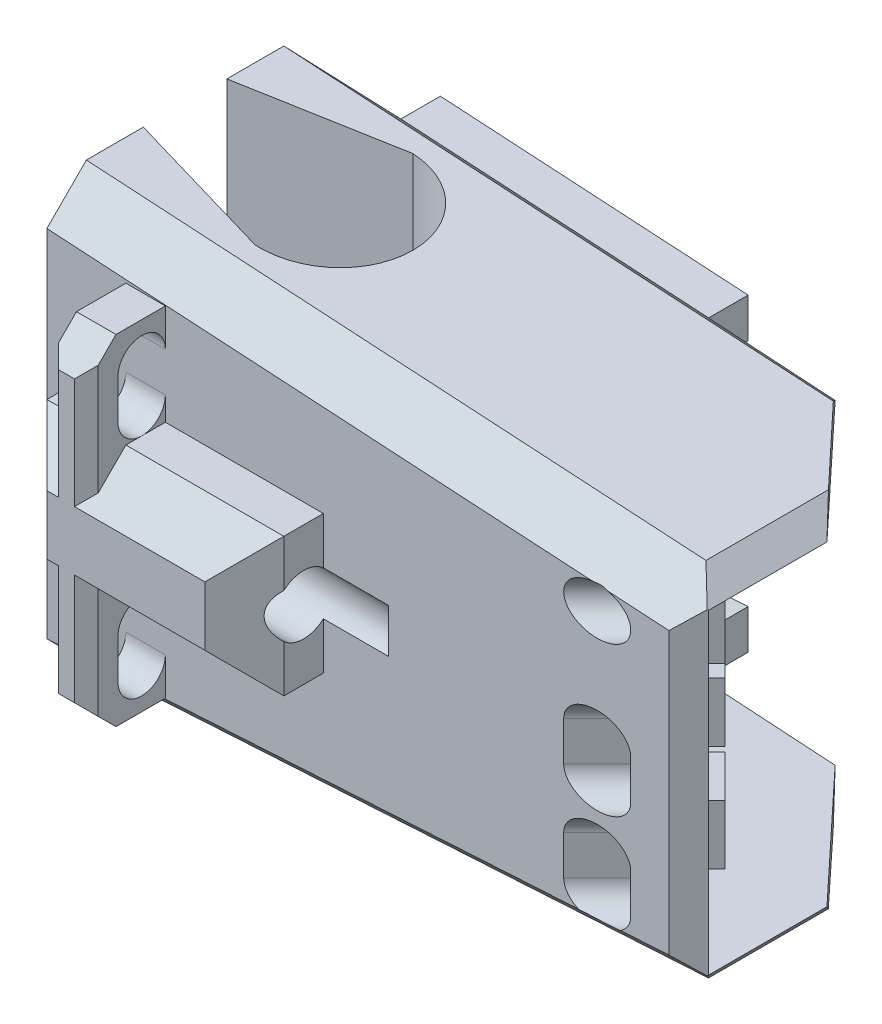
SolidWorks part; units mm, degrees
ref_plane "Front Plane" through (0, 0, 0) normal (0, 0, 1) x (1, 0, 0)
ref_plane "Top Plane" through (0, 0, 0) normal (0, 1, 0) x (1, 0, 0)
ref_plane "Right Plane" through (0, 0, 0) normal (1, 0, 0) x (0, 0, -1)
sketch "Sketch2" plane through (0, 0, 0) normal (0, 0, 1) x (1, 0, 0)
  line L0 (0, 0) -> (0, 11)
  line L1 (0, 11) -> (16.75, 10)
  line L2 (16.75, 10) -> (16.75, 1)
  line L3 (16.75, 1) -> (0, 0)
  dimension "D1" = 9
  dimension "D2" = 11
  dimension "D3" = 16.75
extrude "Boss-Extrude1" add sketch "Sketch2" along normal blind 7
chamfer "Chamfer1" distance 1 angle 45 4 edges at (8.375, 10.5, 0) (8.375, 0.5, 0) (8.375, 0.5, 7) (8.375, 10.5, 7)
chamfer "Chamfer7" distance 1 angle 45 4 edges at (16.75, 5.5, 7) (16.75, 1, 3.5) (16.75, 5.5, 0) (16.75, 10, 3.5)
chamfer "Chamfer14" distance 1 angle 63 1 edges at (0, 5.5, 0)
sketch "Sketch13" plane through (0, 0, 7) normal (0, 0, 1) x (1, 0, 0)
  line L0 (0, 5.5) -> (15.75, 5.5) construction
  line L1 (0, 9.9982) -> (0, 1.0018) construction
  line L2 (15.75, 1.9421) -> (15.75, 9.0579) construction
  line L3 (1, 3.75) -> (7, 3.75)
  line L5 (1, 3.75) -> (1, 7.25)
  line L6 (1, 7.25) -> (7, 7.25)
  line L7 (7, 3.75) -> (7, 7.25)
  point P11 (7, 5.5)
  point P12 (1, 5.5)
  dimension "D1" = 1.75
  dimension "D2" = 6
  dimension "D3" = 1
extrude "Boss-Extrude4" add sketch "Sketch13" along normal blind 2
sketch "Sketch14" plane through (1, 0, 0) normal (-1, 0, 0) x (0, 0, 1)
  line L0 (9, 5.5) -> (7, 5.5) construction
  line L1 (9, 7.25) -> (9, 3.75) construction
  line L2 (7, 7.25) -> (7, 3.75) construction
  circle A0 centre (7.5, 5.5) radius 0.75
  dimension "D1" = 1.5
  dimension "D2" = 1.5
extrude "Cut-Extrude9" cut sketch "Sketch14" against normal blind 7.6473 and the other way blind 2
chamfer "Chamfer15" distance 1 angle 45 4 edges at (4, 3.75, 9) (1, 5.5, 9) (4, 7.25, 9) (7, 5.5, 9)
sketch "Sketch15" plane through (0, 0, 0) normal (0, 0, -1) x (-1, 0, 0)
  line L0 (-1.9626, 5.5) -> (-15.75, 5.5) construction
  line L1 (-1.9626, 1.119) -> (-1.9626, 9.881) construction
  line L2 (-15.75, 9.0579) -> (-15.75, 1.9421) construction
  line L3 (-2.9626, 3.75) -> (-6.9626, 3.75)
  line L5 (-2.9626, 3.75) -> (-2.9626, 7.25)
  line L6 (-2.9626, 7.25) -> (-6.9626, 7.25)
  line L7 (-6.9626, 3.75) -> (-6.9626, 7.25)
  point P11 (-2.9626, 5.5)
  point P12 (-6.9626, 5.5)
  dimension "D1" = 1.75
  dimension "D2" = 1
  dimension "D3" = 4
extrude "Boss-Extrude6" add sketch "Sketch15" along normal blind 2
sketch "Sketch18" plane through (2.9626, 0, 0) normal (-1, 0, 0) x (0, 0, 1)
  line L0 (-2, 5.5) -> (0, 5.5) construction
  line L1 (-2, 3.75) -> (-2, 7.25) construction
  line L2 (0, 3.75) -> (0, 7.25) construction
  circle A0 centre (-0.5, 5.5) radius 0.75
  dimension "D1" = 1.5
  dimension "D2" = 1.5
extrude "Cut-Extrude10" cut sketch "Sketch18" against normal blind 6 and the other way blind 2
chamfer "Chamfer16" distance 1 angle 45 4 edges at (4.9626, 7.25, -2) (2.9626, 5.5, -2) (4.9626, 3.75, -2) (6.9626, 5.5, -2)
ref_plane "Plane1" through (4.875, 0, -4.875) normal (0.7071, 0, -0.7071) x (-0.7071, 0, -0.7071)
sketch "Sketch19" plane through (0, 0, 0) normal (0, 0, -1) x (-1, 0, 0)
  line L0 (-15.75, 5.5) -> (1.3235, 5.5) construction
  line L1 (-15.75, 9.0579) -> (-15.75, 1.9421) construction
  line L2 (-9.7553, 9.5) -> (-17.4165, 9.5)
  line L4 (-9.7553, 9.5) -> (-9.7553, 1.5)
  line L5 (-9.7553, 1.5) -> (-17.4165, 1.5)
  line L6 (-17.4165, 9.5) -> (-17.4165, 1.5)
  point P9 (-17.4165, 5.5)
  point P10 (-9.7553, 5.5)
  dimension "D1" = 4
extrude "Cut-Extrude12" cut sketch "Sketch19" against normal up to surface (0.0053 mm away) up to plane "Plane1"
sketch "Sketch21" plane through (0, 9.5, 0) normal (0, -1, 0) x (1, 0, 0)
  line L0 (16.25, 3.5) -> (16.25, 0.5)
  line L1 (16.25, 0.5) -> (16.25, 6.5) construction
  line L2 (16.25, 0.5) -> (16.25, -4.0591)
  line L3 (16.25, -4.0591) -> (11.3071, -4.0591)
  line L4 (11.3071, -4.0591) -> (13.25, 0.2923)
  line L5 (9.839, 0.089) -> (16.2193, 0.4693) construction
  line L6 (13.25, 0.2923) -> (16.25, 3.5)
  dimension "D1" = 3
extrude "Cut-Extrude14" cut sketch "Sketch21" against normal blind 2 and the other way blind 10
sketch "Sketch23" plane through (4.875, 0, -4.875) normal (0.7071, 0, -0.7071) x (-0.7071, 0, -0.7071)
  line L0 (-6.9018, 5.5) -> (-16.0867, 5.5009) construction
  line L1 (-6.9018, 9.4211) -> (-6.9018, 1.5789) construction
  line L2 (-16.0867, 1.5019) -> (-16.0867, 9.5) construction
  line L3 (-11.5534, 9.5) -> (-11.5522, 1.5) construction
  line L4 (-16.0867, 9.5) -> (-7.0202, 9.5) construction
  line L5 (-7.0202, 1.5) -> (-16.0843, 1.5) construction
  line L6 (-10.4024, 2.5007) -> (-10.4021, 4.0007)
  line L7 (-8.9018, 8.5) -> (-10.4018, 8.5)
  line L8 (-8.9018, 8.5) -> (-8.9018, 7)
  line L9 (-8.9018, 7) -> (-10.4018, 7)
  line L10 (-10.4018, 8.5) -> (-10.4018, 7)
  line L11 (-8.9024, 2.5004) -> (-10.4024, 2.5007)
  line L12 (-8.9024, 2.5004) -> (-8.9021, 4.0004)
  line L13 (-8.9021, 4.0004) -> (-10.4021, 4.0007)
  line L14 (-12.7023, 2.5004) -> (-12.7031, 4.0004)
  line L15 (-14.2023, 2.4996) -> (-12.7023, 2.5004)
  line L16 (-14.2023, 2.4996) -> (-14.2031, 3.9996)
  line L17 (-14.2031, 3.9996) -> (-12.7031, 4.0004)
  line L18 (-14.2048, 8.4992) -> (-12.7048, 8.4997)
  line L19 (-12.7048, 8.4997) -> (-12.7043, 6.9997)
  line L20 (-14.2043, 6.9992) -> (-12.7043, 6.9997)
  line L21 (-14.2048, 8.4992) -> (-14.2043, 6.9992)
  dimension "D1" = 1.5
  dimension "D2" = 2
  dimension "D3" = 1
extrude "Boss-Extrude7" add sketch "Sketch23" along normal blind 0.3
sketch "Sketch30" plane through (0, 0, 7) normal (0, 0, 1) x (1, 0, 0)
  line L0 (6, 6.25) -> (2, 6.25) construction
  line L1 (2, 9.8) -> (3, 9.8)
  line L2 (2, 9.8) -> (2, 6.25)
  line L3 (2, 6.25) -> (3, 6.25)
  line L4 (3, 9.8) -> (3, 6.25)
  line L5 (2, 6.25) -> (2, 4.75) construction
  line L6 (15.75, 5.5) -> (-1.2253, 5.5) construction
  line L7 (15.75, 1.9421) -> (15.75, 9.0579) construction
  line L8 (2, 4.75) -> (3, 4.75)
  line L9 (2, 1.2) -> (3, 1.2)
  line L10 (3, 1.2) -> (3, 4.75)
  line L11 (2, 1.2) -> (2, 4.75)
  dimension "D1" = 0
  dimension "D2" = 3.55
  dimension "D3" = 1
  dimension "D4" = 0
extrude "Boss-Extrude12" add sketch "Sketch30" along normal blind 2
chamfer "Chamfer19" distance 0.3 angle 45 4 edges at (3, 2.975, 9) (2, 2.975, 9) (2, 8.025, 9) (3, 8.025, 9)
chamfer "Chamfer20" distance 0.75 angle 45 2 edges at (2.5, 1.2, 9) (2.5, 9.8, 9)
sketch "Sketch35" plane through (2, 0, 0) normal (-1, 0, 0) x (0, 0, 1)
  line L0 (7.6, 8.85) -> (7.6, 7.85) construction
  line L1 (8.2, 8.85) -> (8.2, 7.85)
  line L2 (7, 8.85) -> (7, 7.85)
  line L3 (7, 9.8) -> (7, 7.25) construction
  line L4 (7, 7.25) -> (8, 7.25) construction
  line L5 (7.6, 3.15) -> (7.6, 2.15) construction
  line L6 (8.2, 3.15) -> (8.2, 2.15)
  line L7 (7, 3.15) -> (7, 2.15)
  line L8 (8, 3.75) -> (7, 3.75) construction
  arc A0 (8.2, 8.85) -> (7, 8.85) centre (7.6, 8.85) ccw
  arc A1 (7, 7.85) -> (8.2, 7.85) centre (7.6, 7.85) ccw
  arc A2 (8.2, 3.15) -> (7, 3.15) centre (7.6, 3.15) ccw
  arc A3 (7, 2.15) -> (8.2, 2.15) centre (7.6, 2.15) ccw
  point P2 (7.6, 8.35)
  point P9 (7.6, 2.65)
  dimension "D1" = 1
  dimension "D2" = 0.6
  dimension "D3" = 0
  dimension "D4" = 0.6
  dimension "D5" = 0.6
extrude "Cut-Extrude32" cut sketch "Sketch35" against normal blind 1.23
ref_plane "Plane2" through (0, 0, 0) normal (0, 1, 0) x (0, 0, -1)
sketch "Sketch36" plane through (0, 0, 0) normal (0, 1, 0) x (0, 0, -1)
  line L0 (-6, 0) -> (-1, 0) construction
  line L1 (-3.5, 0) -> (-3.5, -4.9376) construction
  line L2 (-3.5, -3.77) -> (-3.5, 2.23) construction
  line L3 (-3, 2.23) -> (-4, 2.23)
  line L4 (-4, 2.23) -> (-5.5, -3.77)
  line L5 (-3, 2.23) -> (-1.5, -3.77)
  circle A0 centre (-3.5, -3.77) radius 2
  dimension "D1" = 4
  dimension "D3" = 3.77
  dimension "D4" = 1
  dimension "D5" = 6
extrude "Cut-Extrude33" cut sketch "Sketch36" along normal up to surface (11.1331 mm away) contours A0 L5 L3 L4 | L4 A0 L5
sketch "Sketch38" plane through (4.875, 0, -4.875) normal (0.7071, 0, -0.7071) x (-0.7071, 0, -0.7071)
  line L0 (-14.8028, 5.8) -> (-14.8028, 4.8) construction
  line L1 (-14.2028, 5.8) -> (-14.2028, 4.8)
  line L2 (-15.4028, 5.8) -> (-15.4028, 4.8)
  line L3 (-14.8028, 3.3) -> (-14.8028, 2.3) construction
  line L4 (-14.2028, 3.3) -> (-14.2028, 2.3)
  line L5 (-15.4028, 3.3) -> (-15.4028, 2.3)
  line L6 (-14.8028, 2.3) -> (-14.8028, 8.5797) construction
  line L7 (-7.0202, 1.5) -> (-16.0843, 1.5) construction
  line L8 (-16.0867, 9.5) -> (-7.0202, 9.5) construction
  line L10 (-14.2031, 3.9996) -> (-14.2023, 2.4996) construction
  arc A0 (-14.2028, 5.8) -> (-15.4028, 5.8) centre (-14.8028, 5.8) ccw
  arc A1 (-15.4028, 4.8) -> (-14.2028, 4.8) centre (-14.8028, 4.8) ccw
  arc A2 (-14.2028, 3.3) -> (-15.4028, 3.3) centre (-14.8028, 3.3) ccw
  arc A3 (-15.4028, 2.3) -> (-14.2028, 2.3) centre (-14.8028, 2.3) ccw
  circle A4 centre (-14.8028, 8.5797) radius 0.6
  point P2 (-14.8028, 5.3)
  point P7 (-14.8028, 2.8)
  dimension "D5" = 1.2
  dimension "D1" = 1
  dimension "D2" = 0.6
  dimension "D3" = 1
  dimension "D4" = 0.6
  dimension "D6" = 1.5
  dimension "D7" = 0.8
  dimension "D8" = 0.9203
  dimension "D9" = 0.6
extrude "Cut-Extrude34" cut sketch "Sketch38" against normal up to surface (2.591 mm away)
sketch "Sketch39" plane through (0, 0, 0) normal (0, 0, -1) x (-1, 0, 0)
  line L0 (-1.9626, 9.881) -> (-9.7553, 9.4158)
  line L1 (-9.7553, 9.4158) -> (-9.7553, 8.414)
  line L2 (-9.7553, 1.5842) -> (-9.7553, 9.4158) construction
  line L3 (-9.7553, 8.414) -> (-1.9626, 8.8793)
  line L4 (-1.9626, 6.059) -> (-1.9626, 9.881) construction
  line L5 (-1.9626, 8.8793) -> (-1.9626, 9.881)
  line L6 (-2.9626, 6.6545) -> (-1.9626, 6.6545)
  line L7 (-2.9626, 6.059) -> (-2.9626, 7.25) construction
  line L8 (-1.9626, 6.6545) -> (-1.9626, 8.8793)
  line L9 (-2.9626, 8.8196) -> (-2.9626, 6.6545)
  line L10 (-1.9626, 1.119) -> (-9.7553, 1.5842)
  line L11 (-9.7553, 1.5842) -> (-9.7553, 2.586)
  line L12 (-9.7553, 2.586) -> (-1.9626, 2.1207)
  line L13 (-1.9626, 1.119) -> (-1.9626, 4.941) construction
  line L14 (-1.9626, 2.1207) -> (-1.9626, 1.119)
  line L15 (-2.9626, 4.3455) -> (-2.9626, 2.1804)
  line L16 (-2.9626, 3.75) -> (-2.9626, 4.941) construction
  line L17 (-2.9626, 2.1804) -> (-1.9626, 2.1207)
  line L18 (-1.9626, 4.3455) -> (-2.9626, 4.3455)
  line M1 (-9.7553, 9.4158) -> (-9.7553, 1.5842)
  line M2 (-9.7553, 1.5842) -> (-1.9626, 1.119)
  line M3 (-1.9626, 1.119) -> (-1.9626, 4.941)
  line M5 (-2.9626, 4.941) -> (-2.9626, 3.75)
  line M13 (-2.9626, 7.25) -> (-2.9626, 6.059)
  line M15 (-1.9626, 6.059) -> (-1.9626, 9.881)
  line M16 (-1.9626, 9.881) -> (-9.7553, 9.4158)
  dimension "D1" = 1
  dimension "D2" = 1
extrude "Boss-Extrude13" add sketch "Sketch39" along normal blind 1 contours L18 L15 L12 M3 M5 | L12 M1 M2 M3 | L3 L9 L6 M13 M15 | L3 M1 M15 M16
sketch "Sketch41" plane through (0, 0, 0) normal (0, 0, -1) x (-1, 0, 0)
  line L0 (-8.9694, 7.6957) -> (-7.5673, 7.6957) construction
  line L1 (-8.9694, 8.1957) -> (-7.5673, 8.1957)
  line L2 (-8.9694, 7.1957) -> (-7.5673, 7.1957)
  line L3 (-8.9694, 3.2675) -> (-7.5673, 3.2675) construction
  line L4 (-8.9694, 3.7675) -> (-7.5673, 3.7675)
  line L5 (-8.9694, 2.7675) -> (-7.5673, 2.7675)
  arc A0 (-8.9694, 8.1957) -> (-8.9694, 7.1957) centre (-8.9694, 7.6957) ccw
  arc A1 (-7.5673, 7.1957) -> (-7.5673, 8.1957) centre (-7.5673, 7.6957) ccw
  arc A2 (-8.9694, 3.7675) -> (-8.9694, 2.7675) centre (-8.9694, 3.2675) ccw
  arc A3 (-7.5673, 2.7675) -> (-7.5673, 3.7675) centre (-7.5673, 3.2675) ccw
  point P2 (-8.2683, 7.6957)
  point P7 (-8.2683, 3.2675)
  dimension "D1" = 0.5
extrude "Cut-Extrude35" cut sketch "Sketch41" against normal blind 1
